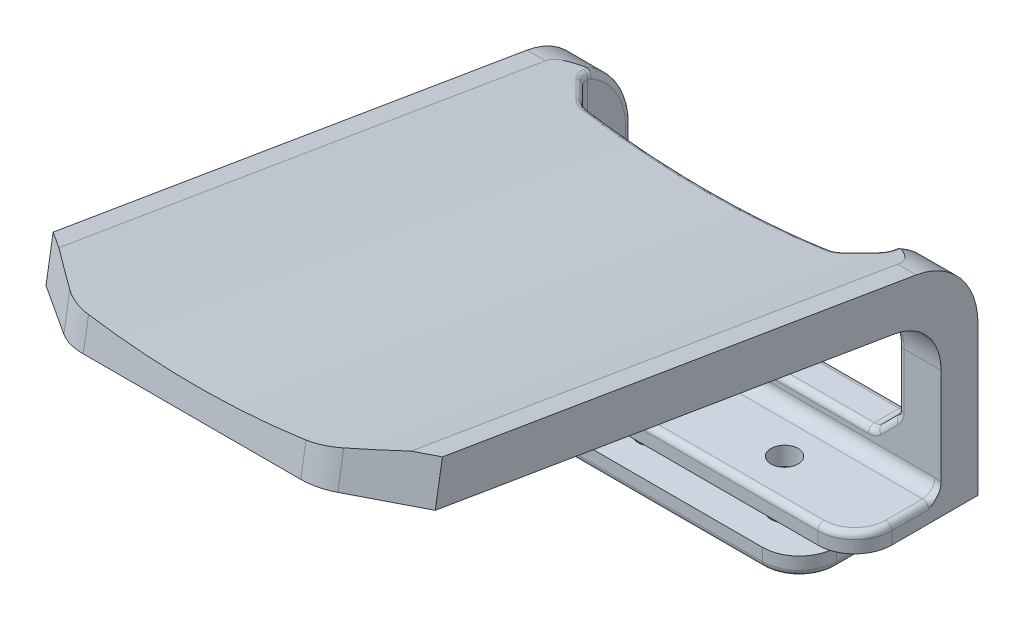
SolidWorks part; units mm, degrees
ref_plane "Front Plane" through (0, 0, 0) normal (0, 0, 1) x (1, 0, 0)
ref_plane "Top Plane" through (0, 0, 0) normal (0, 1, 0) x (1, 0, 0)
ref_plane "Right Plane" through (0, 0, 0) normal (1, 0, 0) x (0, 0, -1)
sketch "Sketch1" plane through (0, 0, 0) normal (0, 1, 0) x (1, 0, 0)
  line L1 (0, 0) -> (15.8, 0)
  line L2 (0, 0) -> (0, -1.5)
  line L3 (0, -1.5) -> (15.8, -1.5)
  line L4 (15.8, 0) -> (15.8, -1.5)
  dimension "D1" = 15.8
  dimension "D2" = 1.5
extrude "Boss-Extrude1" add sketch "Sketch1" along normal blind 9
sketch "Sketch5" plane through (0, 9, 0) normal (0, 1, 0) x (1, 0, 0)
  line L0 (0, 0) -> (0, -1.5) construction
  line L1 (0, 0) -> (15.8, 0)
  line L2 (0, 0) -> (0, -24)
  line L3 (0, -24) -> (15.8, -24)
  line L4 (15.8, 0) -> (15.8, -24)
  line L5 (15.8, -1.5) -> (15.8, 0) construction
  line L6 (15.8, 0) -> (0, 0) construction
  dimension "D1" = 0
  dimension "D2" = 0
  dimension "D4" = 24
extrude "Boss-Extrude4" add sketch "Sketch5" along normal blind 5.5
sketch "Sketch6" plane through (0, 0, 0) normal (-1, 0, 0) x (0, 0, 1)
  line L0 (0, 10.5324) -> (23.7097, 14.5)
  line L1 (0, 14.5) -> (0, 0) construction
  line L2 (24, 14.5) -> (0, 14.5)
  line L3 (0, 14.5) -> (0, 10.5324)
  line L4 (1.5, 9) -> (24, 12.7652)
  line L5 (1.5, 9) -> (24, 9) construction
  line L6 (24, 14.5) -> (24, 9) construction
  line L7 (24, 12.7652) -> (24, 9)
  line L8 (24, 9) -> (1.5, 9)
  line L10 (24, 12.7652) -> (23.7097, 14.5)
  line L11 (24, 14.5) -> (24, 12.7652)
  line L12 (24, 14.5) -> (24, 12.7652)
  line L13 (23.7097, 14.5) -> (24, 12.7652)
  line L14 (24, 14.5) -> (23.7097, 14.5)
  line L15 (1.5, 9) -> (24, 9) construction
  line M6 (1.5, 9) -> (24, 9)
  line M7 (24, 9) -> (24, 14.5)
  line M8 (24, 14.5) -> (0, 14.5)
  line M9 (0, 14.5) -> (0, 0)
  dimension "D2" = 9.5
extrude "Cut-Extrude2" cut sketch "Sketch6" against normal through all both and the other way through all contours L10 L0 M7 M8 M9 | L4 M6 M7 | L10 M7 M8 region at (0, 13.1775, 7.9032) region at (0, 10.2551, 16.5) region at (0, 13.9217, 23.9032)
sketch "Sketch8" plane through (0, 0, 0) normal (0, -1, 0) x (1, 0, 0)
  line L0 (0, 24) -> (0, 1.5) construction
  line L1 (5.75, 11.35) -> (10.3, 11.35)
  line L2 (5.75, 11.35) -> (5.75, 8.6)
  line L3 (5.75, 8.6) -> (10.3, 8.6)
  line L4 (10.3, 11.35) -> (10.3, 8.6)
  line L5 (15.8, 1.5) -> (15.8, 24) construction
  line L6 (0, 1.5) -> (15.8, 1.5) construction
  dimension "D1" = 5.75
  dimension "D2" = 5.5
  dimension "D3" = 7.1
  dimension "D4" = 2.75
extrude "Boss-Extrude5" add sketch "Sketch8" along normal blind 0.6 and the other way blind 1.3 from offset 10 offset against normal yes
sketch "Sketch9" plane through (0, 9.4, 0) normal (0, -1, 0) x (1, 0, 0)
  line L0 (0, 24) -> (0, 1.5) construction
  line L1 (1.75, 3) -> (14.05, 3)
  line L2 (1.75, 3) -> (1.75, -4.1958)
  line L3 (1.75, -4.1958) -> (14.05, -4.1958)
  line L4 (14.05, 3) -> (14.05, -4.1958)
  line L5 (15.8, 1.5) -> (15.8, 24) construction
  line L6 (15.8, 0) -> (0, 0) construction
  dimension "D1" = 1.75
  dimension "D2" = 1.75
  dimension "D3" = 3
extrude "Cut-Extrude3" cut sketch "Sketch9" against normal blind 10 and the other way blind 5.75
sketch "Sketch10" plane through (0, 0, 1.5) normal (0, 0, 1) x (1, 0, 0)
  line L0 (15.8, 9) -> (15.8, 0) construction
  line L1 (0, 0) -> (15.8, 0)
  line L2 (0, 0) -> (0, 0.75)
  line L3 (0, 0.75) -> (15.8, 0.75)
  line L4 (15.8, 0) -> (15.8, 0.75)
  line L5 (0, 9) -> (0, 0) construction
  line L6 (15.8, 2.7) -> (0, 2.7)
  line L7 (15.8, 2.7) -> (15.8, 1.95)
  line L8 (15.8, 1.95) -> (0, 1.95)
  line L9 (0, 2.7) -> (0, 1.95)
  dimension "D1" = 0.75
  dimension "D2" = 0.75
  dimension "D3" = 1.2
extrude "Boss-Extrude6" add sketch "Sketch10" along normal blind 3.5
sketch "Sketch12" plane through (15.8, 0, 0) normal (1, 0, 0) x (0, 0, -1)
  line L1 (-5, 1.95) -> (0, 1.95)
  line L2 (-5, 1.95) -> (-5, 0)
  line L3 (-5, 0) -> (0, 0)
  line L4 (0, 1.95) -> (0, 0)
extrude "Cut-Extrude4" cut sketch "Sketch12" against normal blind 2.25
sketch "Sketch13" plane through (0, 0, 0) normal (0, -1, 0) x (1, 0, 0)
  line L0 (11.25, 3.3) -> (5.85, 3.3) construction
  line L1 (15.8, 5) -> (15.8, 0) construction
  line L2 (13.55, 0) -> (0, 0) construction
  circle A0 centre (11.25, 3.3) radius 0.55
  circle A1 centre (5.85, 3.3) radius 0.55
  dimension "D3" = 1.1
  dimension "D1" = 4.55
  dimension "D2" = 5.4
  dimension "D5" = 3.3
  dimension "D4" = 2
extrude "Cut-Extrude5" cut sketch "Sketch13" against normal blind 3
sketch "Sketch14" plane through (0, 4.2546, 25.4242) normal (0, 0.165, 0.9863) x (1, 0, 0)
  line L0 (7.9, 10.3879) -> (7.9, 9.6379) construction
  line L1 (15.8, 10.3879) -> (0, 10.3879) construction
  line L2 (0.75, 10.3879) -> (15.05, 10.3879)
  line L3 (0, 8.629) -> (0, 10.3879) construction
  line L4 (15.8, 8.629) -> (15.8, 10.3879) construction
  spline S0 degree 2 poles (0.75, 10.3879) (7.9, 8.8879) (15.05, 10.3879) knots 0 0 0 1 1 1
  dimension "D1" = 0.75
  dimension "D2" = 0.75
  dimension "D3" = 0.75
extrude "Cut-Extrude6" cut sketch "Sketch14" against normal through all both and the other way through all
chamfer "Chamfer4" distance 2.75 angle 30 2 edges at (5.75, 10.4182, 9.975) (10.3, 10.4182, 9.975) first distance on face at (8.025, 10.4182, 9.975)
fillet "Fillet1" radius 1.5 1 edges at (13.55, 1.35, 1.5)
chamfer "Chamfer5" distance 1 angle 45 2 edges at (14.05, 10.0438, 3) (1.75, 10.0438, 3)
chamfer "Chamfer6" distance 1 angle 45 2 edges at (1.75, 3.65, 0.75) (14.05, 3.65, 0.75)
fillet "Fillet2" radius 0.5 8 edges at (14.05, 4.65, 0.75) (13.05, 3.65, 0.75) (2.75, 3.65, 0.75) (1.75, 4.65, 0.75) (1.75, 9.8764, 2) (14.05, 9.8764, 2) (13.05, 9.9597, 3) (2.75, 9.9597, 3)
chamfer "Chamfer7" distance 3 angle 45 2 edges at (0, 0.375, 5) (0, 2.325, 5)
fillet "Fillet4" radius 3 2 edges at (0.375, 10.5324, 0) (15.425, 10.5324, 0)
fillet "Fillet5" radius 2.25 1 edges
fillet "Fillet6" radius 0.25 38 edges at (13.0682, 9.1968, 2.9463) (13.5733, 8.9503, 2.4767) (13.9874, 8.5518, 2.0351) (14.05, 7.6693, 1.5745) (14.05, 5.9762, 1.5) (14.0119, 4.6658, 1.5) (13.55, 4.15, 1.5) (13.0342, 3.6881, 1.5) (7.9, 3.65, 1.5) (2.7658, 3.6881, 1.5) (2.25, 4.15, 1.5) (1.7881, 4.6658, 1.5) (1.75, 5.9762, 1.5) (1.75, 7.6693, 1.5745) (1.7915, 8.5, 1.9924) (2.2267, 8.9503, 2.4767) (2.8, 9.2074, 2.9747) (1.75, 9.4864, 0.3983) (1.75, 6.4249, 0) (1.7881, 4.6658, 0) (2.25, 4.15, 0) (2.7658, 3.6881, 0) (7.9, 3.65, 0) (13.0342, 3.6881, 0) (13.55, 4.15, 0) (14.0119, 4.6658, 0) (14.05, 6.4249, 0) (14.05, 9.4864, 0.3983) (7.9, 9.2166, 3) (14.05, 10.609, 1.6401) (14.0228, 10.6568, 1.9556) (13.0623, 10.6619, 2.9493) (1.75, 10.609, 1.6401) (1.801, 10.6621, 2.013) (2.7937, 10.6572, 2.9725) (10.4222, 10.3686, 3)
chamfer "Chamfer8" distance 2 angle 55 2 edges at (0, 13.6326, 23.8548) (15.8, 13.6326, 23.8548) first distance on face at (0, 5.6247, 5.4968) first distance on face at (15.8, 7.2722, 6.5644)
fillet "Fillet7" radius 1.5 2 edges at (13.55, 0.375, 5) (15.8, 2.325, 5)
fillet "Fillet9" radius 0.25 6 edges at (13.55, 0, 1.75) (13.1107, 0, 4.5607) (7.525, 0, 5) (15.8, 2.7, 2.5) (15.3607, 2.7, 4.5607) (8.65, 2.7, 5)
fillet "Fillet8" radius 0.5 2 edges at (7.775, 2.7, 1.5) (15.7268, 2.6268, 1.5)
fillet "Fillet10" radius 2 2 edges at (12.9437, 13.4468, 23.8859) (2.8563, 13.4468, 23.8859)
